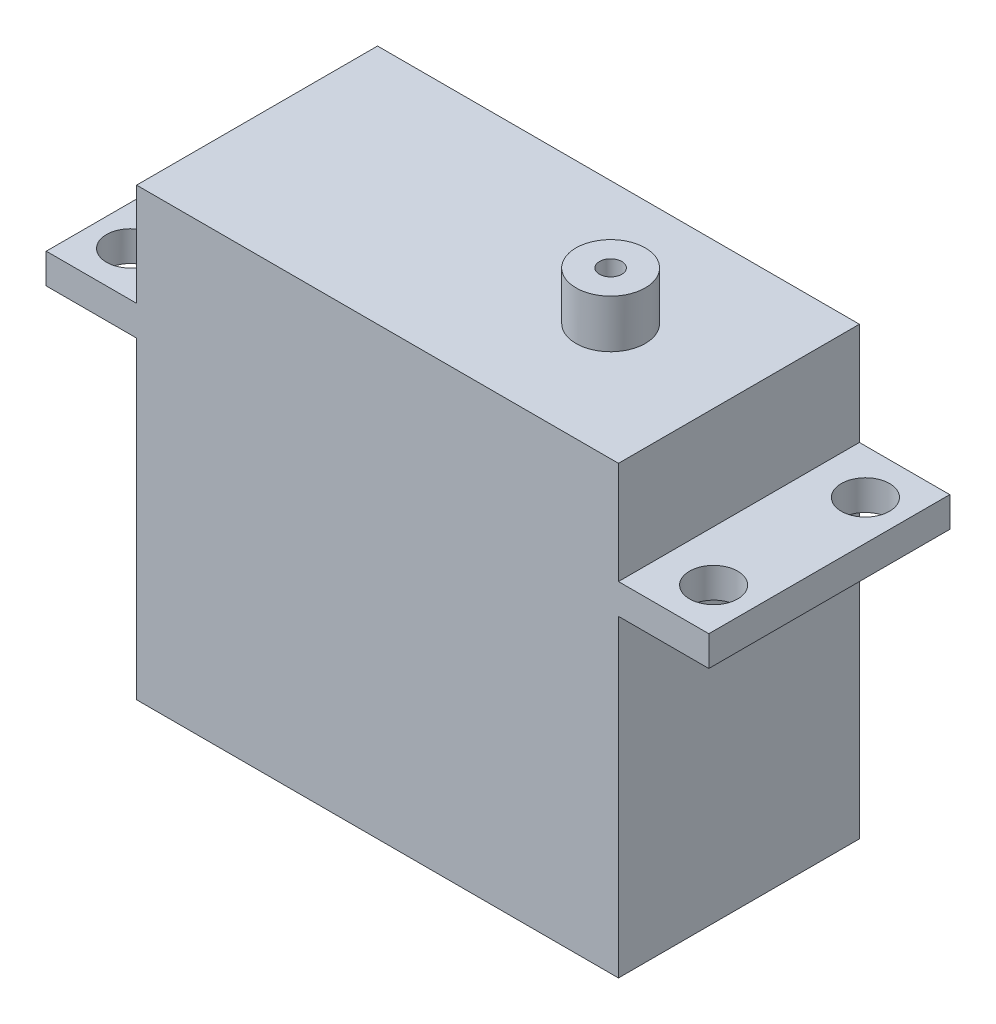
SolidWorks part; units mm, degrees
ref_plane "Front Plane" through (0, 0, 0) normal (0, 0, 1) x (1, 0, 0)
ref_plane "Top Plane" through (0, 0, 0) normal (0, 1, 0) x (1, 0, 0)
ref_plane "Right Plane" through (0, 0, 0) normal (1, 0, 0) x (0, 0, -1)
sketch "Sketch1" plane through (0, 0, 0) normal (0, 1, 0) x (1, 0, 0)
  line L1 (-20, -10) -> (20, -10)
  line L2 (-20, -10) -> (-20, 10)
  line L3 (-20, 10) -> (20, 10)
  line L4 (20, -10) -> (20, 10)
  line L5 (-20, -10) -> (20, 10) construction
  line L6 (-20, 10) -> (20, -10) construction
  point P0 (0, 0)
  dimension "D1" = 20
  dimension "D2" = 40
extrude "Body" add sketch "Sketch1" along normal blind 37
ref_plane "Plane1" through (0, 26, 0) normal (0, 1, 0) x (1, 0, 0)
sketch "Sketch2" plane through (0, 26, 0) normal (0, 1, 0) x (1, 0, 0)
  line L0 (-20, -10) -> (20, -10) construction
  line L1 (20, 10) -> (27.5, 10)
  line L2 (20, 10) -> (20, -10)
  line L3 (20, -10) -> (27.5, -10)
  line L4 (27.5, 10) -> (27.5, -10)
  line L5 (0, -14.3) -> (0, 14.3) construction
  line L6 (-20, -10) -> (-27.5, -10)
  line L7 (-27.5, 10) -> (-27.5, -10)
  line L8 (-20, 10) -> (-27.5, 10)
  line L9 (-20, 10) -> (-20, -10)
  dimension "D1" = 7.5
extrude "Flanges" add sketch "Sketch2" along normal blind 2.5
hole_wizard "Flange Holes" positions "Sketch3" profile "Sketch4" hole size "Ø4.0" standard "ANSI Metric" end condition through all
sketch "Sketch3" plane through (0, 28.5, 0) normal (0, 1, 0) x (1, 0, 0)
  line L1 (-24.2, 6.3) -> (24.2, 6.3) construction
  line L2 (-24.2, 6.3) -> (-24.2, -6.3) construction
  line L3 (-24.2, -6.3) -> (24.2, -6.3) construction
  line L4 (24.2, 6.3) -> (24.2, -6.3) construction
  line L5 (-27.5, 10) -> (-27.5, -10) construction
  line L6 (27.5, -10) -> (27.5, 10) construction
  line L7 (-27.5, 0) -> (27.5, 0) construction
  line L9 (-20, 10) -> (-27.5, 10) construction
  point P0 (-24.2, -6.3)
  point P2 (-24.2, 6.3)
  point P4 (24.2, 6.3)
  point P6 (24.2, -6.3)
  point P59 (-24.2, 0)
  dimension "D1" = 3.3
  dimension "D2" = 3.3
  dimension "D3" = 3.7
  dimension "D4" = 12.6
  dimension "D5" = 48.4
sketch "Sketch4" plane through (-24.2, 28.5, 6.3) normal (1, 0, 0) x (0, 0, 1)
  line L0 (0, 0) -> (0, 28.5)
  line L1 (0, 28.5) -> (2, 28.5)
  line L2 (2, 28.5) -> (2, 0)
  line L5 (2, 0) -> (0, 0)
  line L11 (0, -6.35) -> (0, 107.95) construction
  dimension "Thru Hole Dia." = 4
  dimension "Thru Hole Depth" = 28.5
sketch "Sketch5" plane through (0, 37, 0) normal (0, 1, 0) x (1, 0, 0)
  line L1 (-20, -10) -> (20, -10) construction
  line L2 (20, 10) -> (20, -10) construction
  circle A0 centre (9.625, -0.275) radius 2.875
  dimension "D1" = 5.75
  dimension "D2" = 9.725
  dimension "D3" = 10.375
extrude "Axle" add sketch "Sketch5" along normal blind 4
hole_wizard "Axle Center Hole" positions "Sketch6" profile "Sketch7" hole size "Ø1.85" standard "ANSI Metric"
sketch "Sketch6" plane through (0, 41, 0) normal (0, 1, 0) x (1, 0, 0)
  line L0 (9.625, 2.6) -> (9.625, -3.15) construction
  line L2 (6.75, -0.275) -> (12.5, -0.275) construction
  circle A0 centre (9.625, -0.275) radius 2.875 construction
  circle A1 centre (9.625, -0.275) radius 2.875 construction
  point P0 (9.625, -0.275)
  point P16 (9.625, -0.275)
sketch "Sketch7" plane through (9.625, 41, 0.275) normal (1, 0, 0) x (0, 0, 1)
  line L0 (0, 0) -> (0, 4.5558)
  line L1 (0, 4.5558) -> (0.925, 4)
  line L2 (0.925, 4) -> (0.925, 0)
  line L5 (0.925, 0) -> (0, 0)
  line L10 (0, 4.5558) -> (-0.925, 4) construction
  line L11 (0, -6.35) -> (0, 107.95) construction
  dimension "Hole Dia." = 1.85
  dimension "Hole Depth" = 4
  dimension "Drill Angle" = 118
equation "\"D1@Sketch2\"=(55-40)/2"
equation "\"D1@Sketch3\"=1.3 + 2"
equation "\"D2@Sketch3\"=\"D1@Sketch3\""
equation "\"D3@Sketch3\"= 1.7 + 2"
equation "\"D2@Sketch5\"=(\"D1@Sketch5\"/2) + 6.85"
equation "\"D3@Sketch5\"=(\"D1@Sketch5\"/2) + 7.5"
equation "\"D1@Axle\"=41-37mm"
